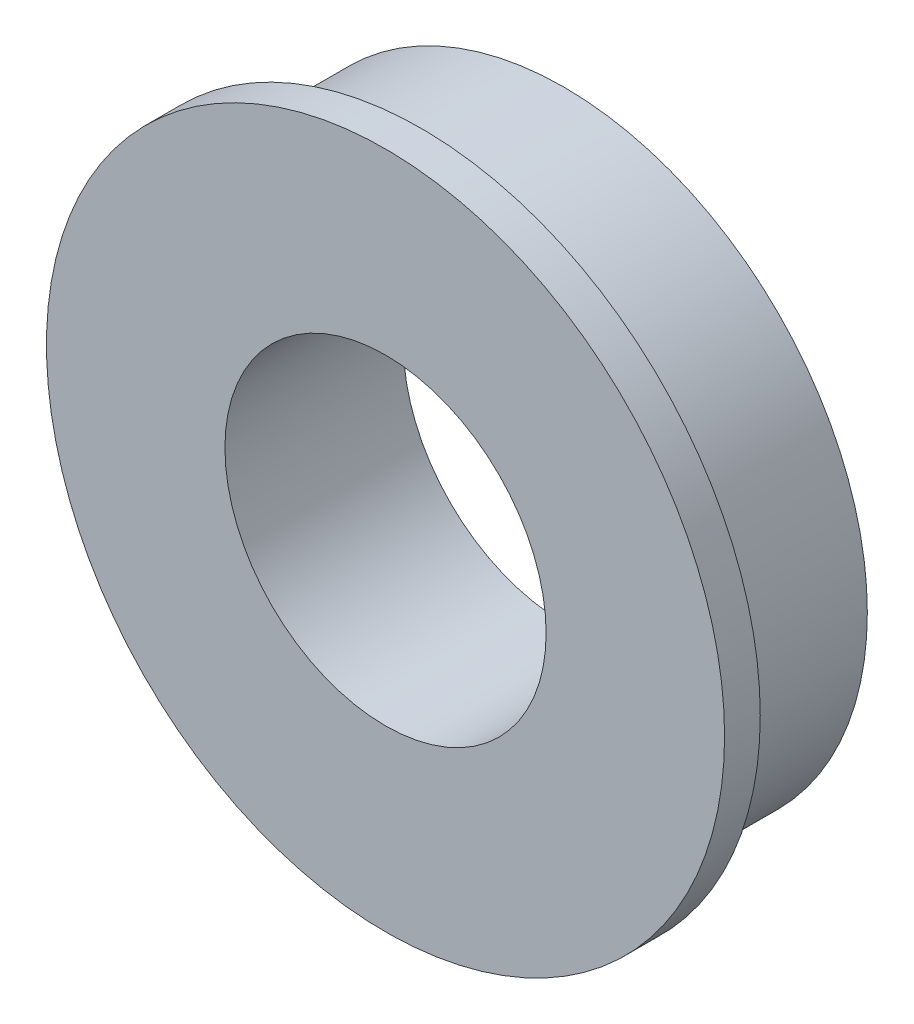
SolidWorks part; units mm, degrees
ref_plane "Front Plane" through (0, 0, 0) normal (0, 0, 1) x (1, 0, 0)
ref_plane "Top Plane" through (0, 0, 0) normal (0, 1, 0) x (1, 0, 0)
ref_plane "Right Plane" through (0, 0, 0) normal (1, 0, 0) x (0, 0, -1)
sketch "Sketch1" plane through (0, 0, 0) normal (0, 0, 1) x (1, 0, 0)
  circle A0 centre (0, 0) radius 8.5
  circle A1 centre (0, 0) radius 4.5
  dimension "D1" = 9
  dimension "D2" = 17
extrude "Boss-Extrude1" add sketch "Sketch1" along normal blind 4
sketch "Sketch2" plane through (0, 0, 4) normal (0, 0, 1) x (1, 0, 0)
  circle A0 centre (0, 0) radius 9.5
  circle A1 centre (0, 0) radius 4.5
  circle A2 centre (0, 0) radius 4.5 construction
  dimension "D1" = 19
extrude "Boss-Extrude2" add sketch "Sketch2" along normal blind 1
